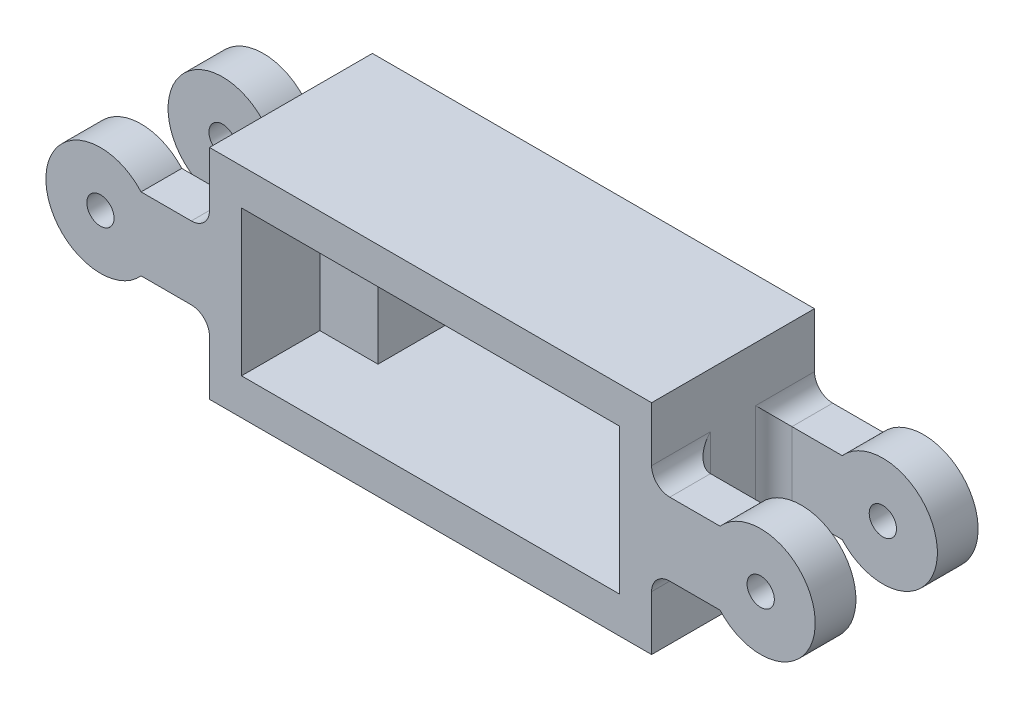
SolidWorks part; units mm, degrees
material "ABS"
ref_plane "Front Plane" through (0, 0, 0) normal (0, 0, 1) x (1, 0, 0)
ref_plane "Top Plane" through (0, 0, 0) normal (0, 1, 0) x (1, 0, 0)
ref_plane "Right Plane" through (0, 0, 0) normal (1, 0, 0) x (0, 0, -1)
sketch "Sketch3" plane through (0, 0, 0) normal (0, 0, 1) x (1, 0, 0)
  line L1 (0, 0) -> (38.608, 0)
  line L2 (0, 0) -> (0, 19.05)
  line L3 (0, 19.05) -> (38.608, 19.05)
  line L4 (38.608, 0) -> (38.608, 19.05)
  line L5 (7.874, 15.875) -> (30.734, 15.875)
  line L6 (7.874, 15.875) -> (7.874, 3.175)
  line L7 (7.874, 3.175) -> (30.734, 3.175)
  line L8 (30.734, 15.875) -> (30.734, 3.175)
  dimension "D1" = 38.608
  dimension "D2" = 19.05
  dimension "D3" = 22.86
  dimension "D4" = 12.7
  dimension "D5" = 3.175
  dimension "D6" = 7.874
extrude "Boss-Extrude1" add sketch "Sketch3" against normal blind 14.224
ref_plane "MirrorPlan2" through (19.304, 0, 0) normal (-1, 0, 0) x (0, 0, 1)
ref_plane "MirrorPlan1" through (0, 0, -7.112) normal (0, 0, 1) x (1, 0, 0)
sketch "Sketch5" plane through (0, 0, 0) normal (0, 0, 1) x (1, 0, 0)
  line L0 (7.874, 3.175) -> (30.734, 3.175) construction
  line L1 (7.874, 15.875) -> (2.794, 15.875)
  line L2 (7.874, 15.875) -> (7.874, 3.175)
  line L3 (7.874, 3.175) -> (2.794, 3.175)
  line L4 (2.794, 15.875) -> (2.794, 3.175)
  line L5 (35.814, 15.875) -> (30.734, 15.875)
  line L6 (35.814, 15.875) -> (35.814, 3.175)
  line L7 (35.814, 3.175) -> (30.734, 3.175)
  line L8 (30.734, 15.875) -> (30.734, 3.175)
  line L9 (30.734, 15.875) -> (7.874, 15.875) construction
  line L10 (30.734, 3.175) -> (30.734, 15.875) construction
  dimension "D1" = 0
  dimension "D2" = 5.08
  dimension "D3" = 0
  dimension "D4" = 0
extrude "Cut-Extrude1" cut sketch "Sketch5" against normal blind 6.8402
sketch "Sketch6" plane through (0, 0, -6.8402) normal (0, 0, 1) x (1, 0, 0)
  line L0 (2.794, 15.875) -> (2.794, 3.175) construction
  line L1 (7.874, 15.875) -> (2.794, 15.875) construction
  line L2 (2.794, 3.175) -> (35.814, 3.175) construction
  circle A0 centre (5.588, 9.525) radius 0.508
  circle A1 centre (33.3883, 9.525) radius 0.508
  dimension "D1" = 2.794
  dimension "D2" = 6.35
  dimension "D3" = 27.8003
  dimension "D4" = 6.35
extrude "Cut-Extrude2" cut sketch "Sketch6" against normal offset from surface (5.7963 mm away) 1.5875 up to face at (19.304, 9.525, -14.224)
sketch "Sketch8" plane through (0, 0, 0) normal (0, 0, 1) x (1, 0, 0)
  line L0 (0, 12.7) -> (-5.9752, 12.7)
  line L1 (0, 6.35) -> (0, 12.7)
  line L2 (0, 6.35) -> (-5.9752, 6.35)
  line L3 (0, 19.05) -> (0, 0) construction
  line L4 (0, 0) -> (38.608, 0) construction
  arc A0 (-5.9752, 6.35) -> (-5.9752, 12.7) centre (-9.525, 9.525) cw
  circle A1 centre (-9.525, 9.525) radius 1.1906
  dimension "D3" = 2.3812
  dimension "D1" = 0
  dimension "D2" = 6.35
extrude "Boss-Extrude2" add sketch "Sketch8" against normal blind 3.556
mirror "Mirror1" about plane through (0, 0, -7.112) normal (0, 0, 1) of "Boss-Extrude2"
mirror "Mirror2" about plane through (19.304, 0, 0) normal (-1, 0, 0) of "Mirror1"
fillet "Fillet1" radius 1.5875 12 edges at (0, 6.35, -1.778) (0, 9.525, -3.556) (0, 12.7, -1.778) (38.608, 12.7, -12.446) (38.608, 12.7, -1.778) (38.608, 9.525, -10.668) (38.608, 9.525, -3.556) (38.608, 6.35, -1.778) (38.608, 6.35, -12.446) (0, 12.7, -12.446) (0, 9.525, -10.668) (0, 6.35, -12.446)
